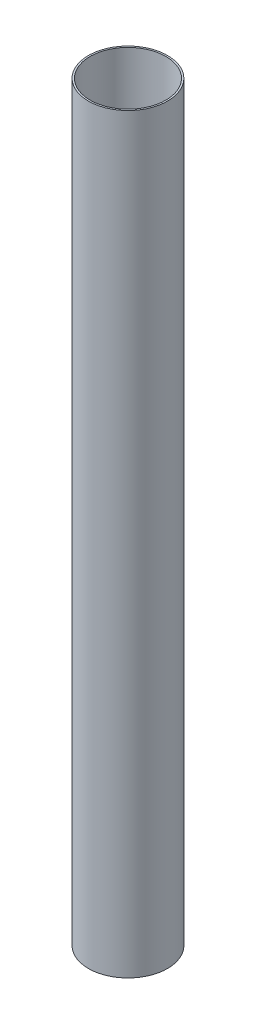
SolidWorks part; units mm, degrees
material "Ceramic Porcelain"
ref_plane "Front" through (0, 0, 0) normal (0, 0, 1) x (1, 0, 0)
ref_plane "Top" through (0, 0, 0) normal (0, 1, 0) x (1, 0, 0)
ref_plane "Right" through (0, 0, 0) normal (1, 0, 0) x (0, 0, -1)
sketch "Sketch1" plane through (0, 0, 0) normal (0, 1, 0) x (1, 0, 0)
  circle A0 centre (0, 0) radius 304.8
  circle A1 centre (0, 0) radius 292.1
  dimension "D1" = 609.6
  dimension "D2" = 584.2
extrude "Boss-Extrude1" add sketch "Sketch1" along normal blind 5791.2
